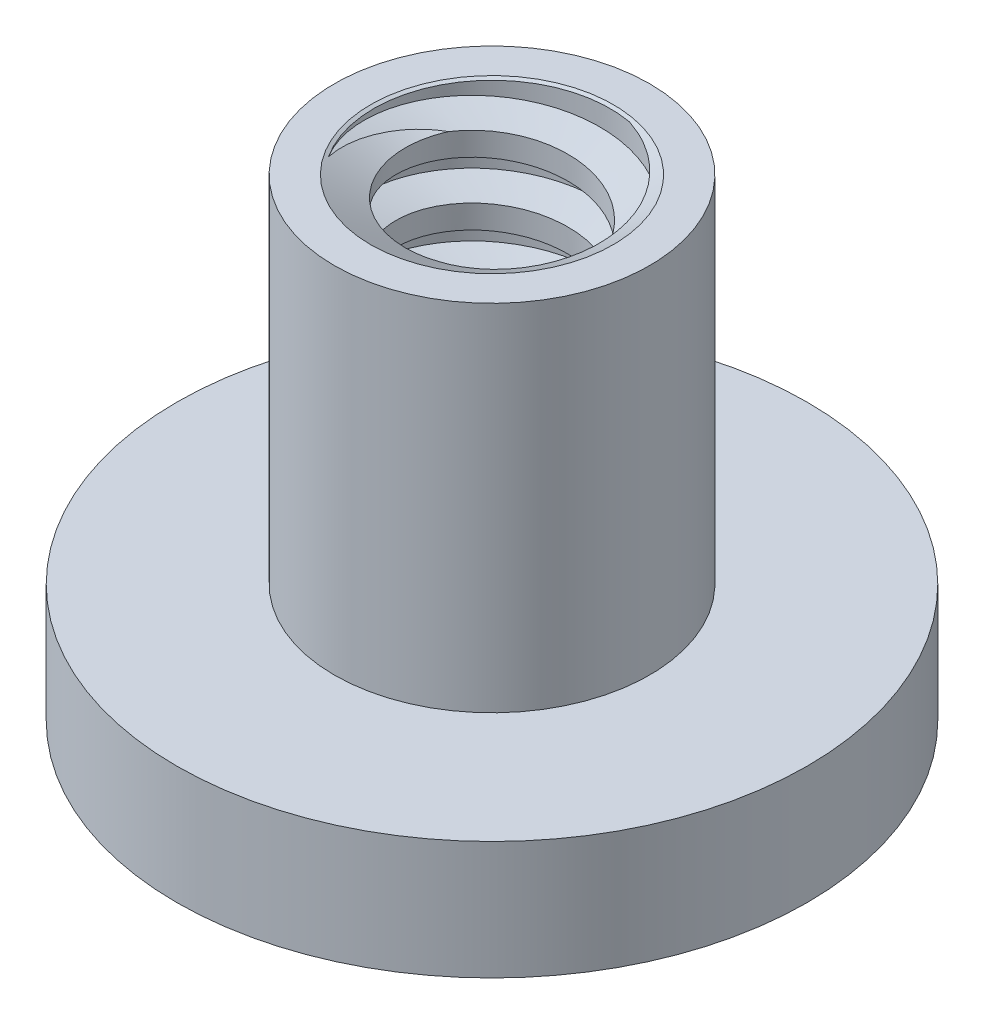
SolidWorks part; units mm, degrees
ref_plane "Front Plane" through (0, 0, 0) normal (0, 0, 1) x (1, 0, 0)
ref_plane "Top Plane" through (0, 0, 0) normal (0, 1, 0) x (1, 0, 0)
ref_plane "Right Plane" through (0, 0, 0) normal (1, 0, 0) x (0, 0, -1)
sketch "Sketch1" plane through (0, 0, 0) normal (0, 1, 0) x (1, 0, 0)
  circle A0 centre (0, 0) radius 25.4
  circle A1 centre (0, 0) radius 12.7 construction
  circle A2 centre (0, 0) radius 9.525 construction
  dimension "D1" = 25.4
  dimension "OD" = 50.8
  dimension "Thread OD" = 19.05
extrude "Boss-Extrude1" add sketch "Sketch1" along normal blind 38.1
sketch "Sketch2" plane through (0, 38.1, 0) normal (0, 1, 0) x (1, 0, 0)
  circle A0 centre (0, 0) radius 9.525 construction
  circle A1 centre (0, 0) radius 9.525
extrude "Cut-Extrude1" cut sketch "Sketch2" against normal up to next
sketch "Sketch3" plane through (0, 38.1, 0) normal (0, 1, 0) x (1, 0, 0)
  circle A1 centre (0, 0) radius 9.525
  circle A2 centre (0, 0) radius 9.525
  point P0 (0, 9.525)
  dimension "D1" = 0
curve "Helix/Spiral1" pitch 5.08 height 43.18 turns 8.5 parameters "Pitch"=5.08
sketch "Sketch4" plane through (0, 0, 0) normal (1, 0, 0) x (0, 0, -1)
  line L0 (9.525, 41.2969) -> (6.985, 40.64)
  line L1 (6.985, 40.64) -> (6.985, 38.7569)
  line L2 (6.985, 38.7569) -> (9.525, 38.1)
  line L3 (9.525, 38.1) -> (9.525, 41.2969)
  line L4 (8.255, 40.9684) -> (8.255, 38.4284) construction
  line L7 (6.985, 39.6984) -> (9.525, 39.6984) construction
  line L8 (9.525, 38.1) -> (9.525, 36.2169) construction
  dimension "a" = 14.5
  dimension "2A" = 29
  dimension "p" = 5.08
  dimension "t" = 2.54
  dimension "h" = 2.54
sweep "Sweep1" add profiles "Sketch4" path "Helix/Spiral1"
sketch "Sketch5" plane through (0, 38.1, 0) normal (0, 1, 0) x (1, 0, 0)
  line L0 (-6.9148, 6.9148) -> (0, 0) construction
  line L1 (0, 0) -> (0, 9.779) construction
  circle A0 centre (0, 0) radius 9.525 construction
  circle A1 centre (0, 0) radius 9.779
  dimension "D2" = 45
  dimension "D1" = 0.254
extrude "Cut-Extrude3" cut sketch "Sketch5" against normal through all draft 60 and the other way through all draft 60
sketch "Sketch6" plane through (0, 0, 0) normal (0, -1, 0) x (1, 0, 0)
  circle A1 centre (0, 0) radius 9.779
  circle A2 centre (0, 0) radius 9.779
  dimension "D1" = 0
extrude "Cut-Extrude4" cut sketch "Sketch6" against normal through all draft 60 and the other way through all draft 60
sketch "Sketch7" plane through (0, 38.1, 0) normal (0, 1, 0) x (1, 0, 0)
  circle A0 centre (0, 0) radius 12.7 construction
  circle A2 centre (0, 0) radius 12.7
extrude "Cut-Extrude5" cut sketch "Sketch7" against normal offset from surface (28.575 mm away) 9.525 flip side to cut up to face at (0, 0, 9.779)
equation "\"D3@Helix/Spiral1\" = \"Pitch@Helix/Spiral1\" + \"Ht.@Boss-Extrude1\""
equation "\"p@Sketch4\" = \"Pitch@Helix/Spiral1\""
equation "\"h@Sketch4\" = \"p@Sketch4\" / 2"
equation "\"t@Sketch4\" = \"p@Sketch4\" / 2"
equation "\"D1@Sketch5\" = \"Pitch@Helix/Spiral1\" * 0.05"
